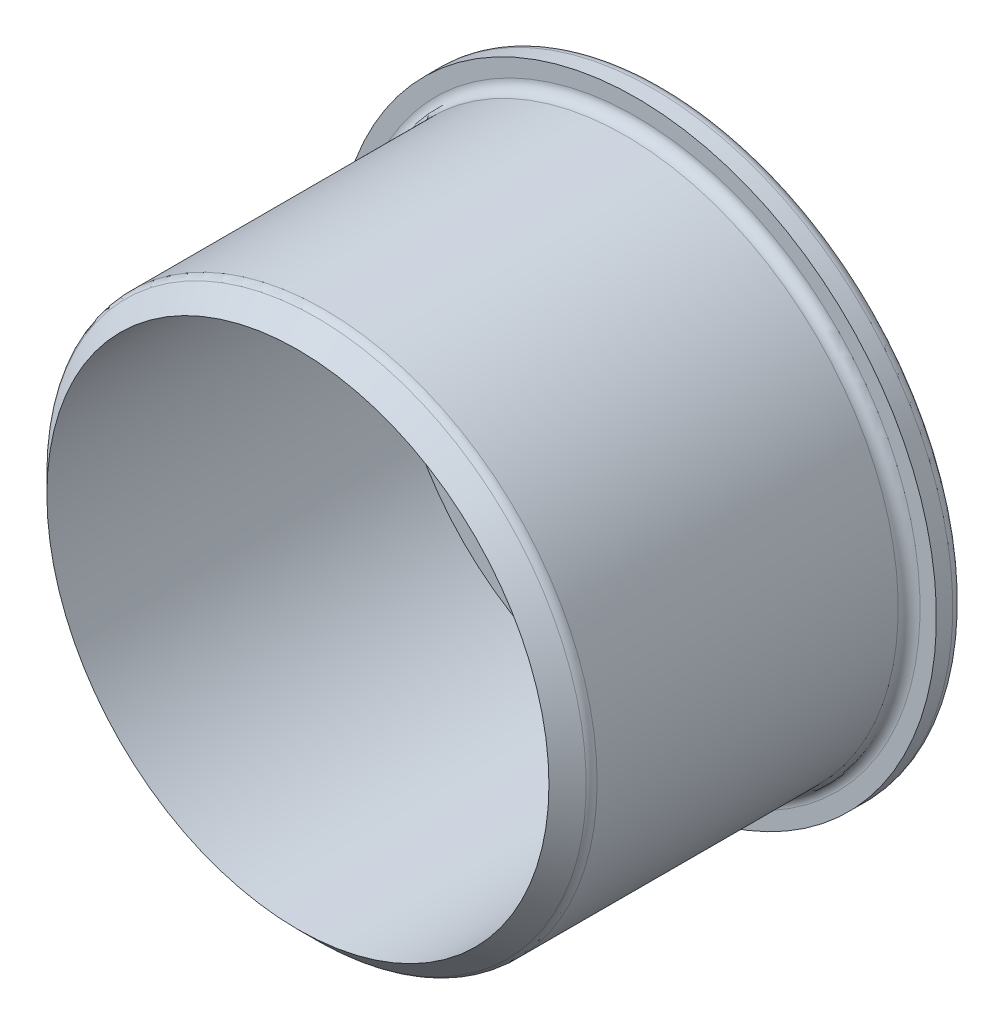
SolidWorks part; units mm, degrees
ref_plane "Спереди" through (0, 0, 0) normal (0, 0, 1) x (1, 0, 0)
ref_plane "Сверху" through (0, 0, 0) normal (0, 1, 0) x (1, 0, 0)
ref_plane "Справа" through (0, 0, 0) normal (1, 0, 0) x (0, 0, -1)
sketch "Эскиз1" plane through (0, 0, 0) normal (0, 0, 1) x (1, 0, 0)
  circle A0 centre (0, 0) radius 25
  dimension "D1" = 50
extrude "Бобышка-Вытянуть1" add sketch "Эскиз1" along normal blind 32 contours A0
sketch "Эскиз2" plane through (0, 0, 0) normal (0, 0, -1) x (-1, 0, 0)
  circle A0 centre (0, 0) radius 27.5
  dimension "D1" = 55
extrude "Бобышка-Вытянуть2" add sketch "Эскиз2" along normal blind 2.5
sketch "Эскиз3" plane through (0, 0, 32) normal (0, 0, 1) x (1, 0, 0)
  circle A0 centre (0, 0) radius 23
  dimension "D1" = 46
extrude "Вырез-Вытянуть1" cut sketch "Эскиз3" against normal blind 32.5
chamfer "Фаска1" distance 3 angle 45 1 edges at (25, 0, 32)
fillet "Скругление1" radius 1 1 edges at (25, 0, 29)
fillet "Скругление2" radius 1 1 edges at (25, 0, 0)
fillet "Скругление3" radius 1 1 edges at (-27.5, 0, -2.5)
sketch "Эскиз4" plane through (0, 0, -2.5) normal (0, 0, -1) x (-1, 0, 0)
  circle A0 centre (0, 0) radius 1.6
  dimension "D1" = 3.2
extrude "Вырез-Вытянуть2" cut sketch "Эскиз4" against normal blind 32.5
